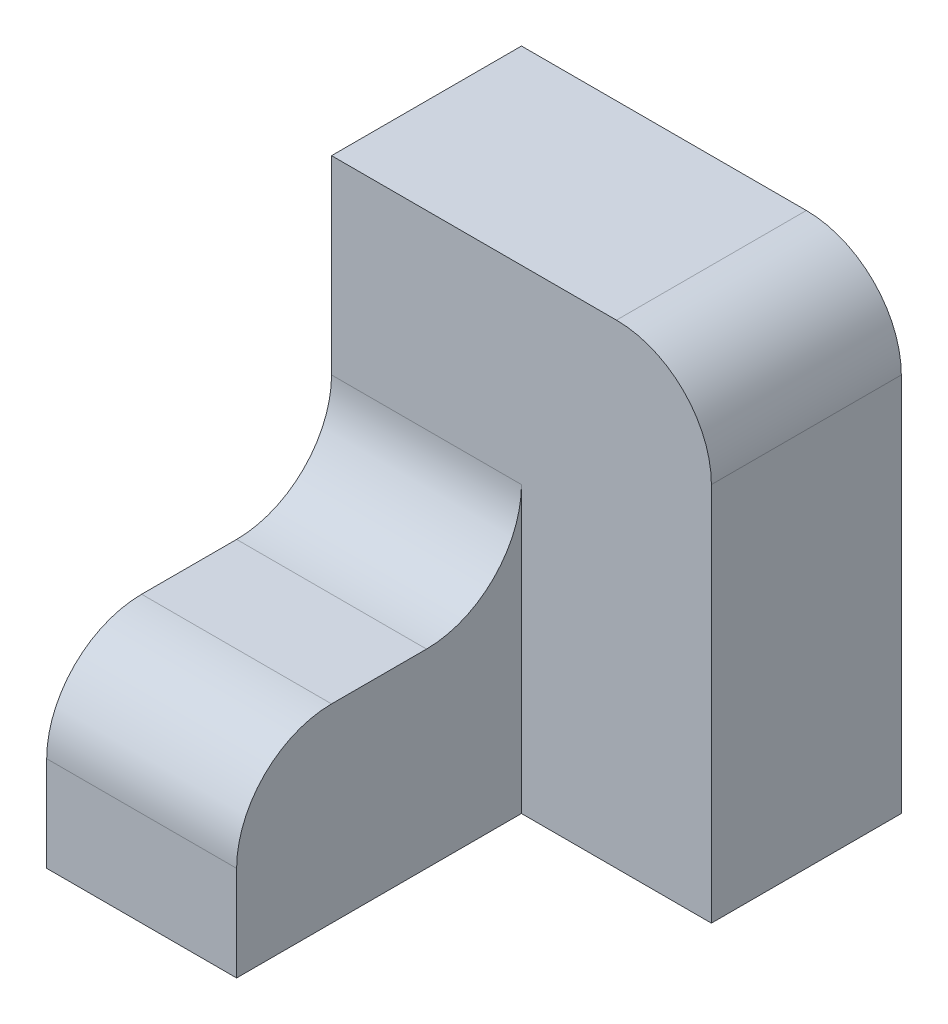
SolidWorks part; units mm, degrees
ref_plane "Front Plane" through (0, 0, 0) normal (0, 0, 1) x (1, 0, 0)
ref_plane "Top Plane" through (0, 0, 0) normal (0, 1, 0) x (1, 0, 0)
ref_plane "Right Plane" through (0, 0, 0) normal (1, 0, 0) x (0, 0, -1)
sketch "Sketch1" plane through (0, 0, 0) normal (0, 1, 0) x (1, 0, 0)
  line L0 (0, 0) -> (0, 30)
  line L1 (0, 30) -> (40, 30)
  line L2 (40, 30) -> (40, 50)
  line L3 (40, 50) -> (0, 50)
  line L4 (0, 50) -> (0, 30)
  line L5 (0, 0) -> (20, 0)
  line L6 (20, 0) -> (20, 30)
  dimension "D1" = 20
  dimension "D2" = 30
  dimension "D3" = 20
extrude "Boss-Extrude1" add sketch "Sketch1" along normal blind 50 contours L1 L2 L3 L4
extrude "Boss-Extrude4" add sketch "Sketch1<6>" along normal blind 20 contours L5 L6 L1 L0 region at (10, 0, -15)
sketch "Sketch1<6>" plane through (0, 0, 0) normal (0, 1, 0) x (1, 0, 0) same geometry as "Sketch1"
fillet "Fillet2" radius 10 3 edges at (40, 50, -40) (10, 20, -30) (10, 20, 0)
